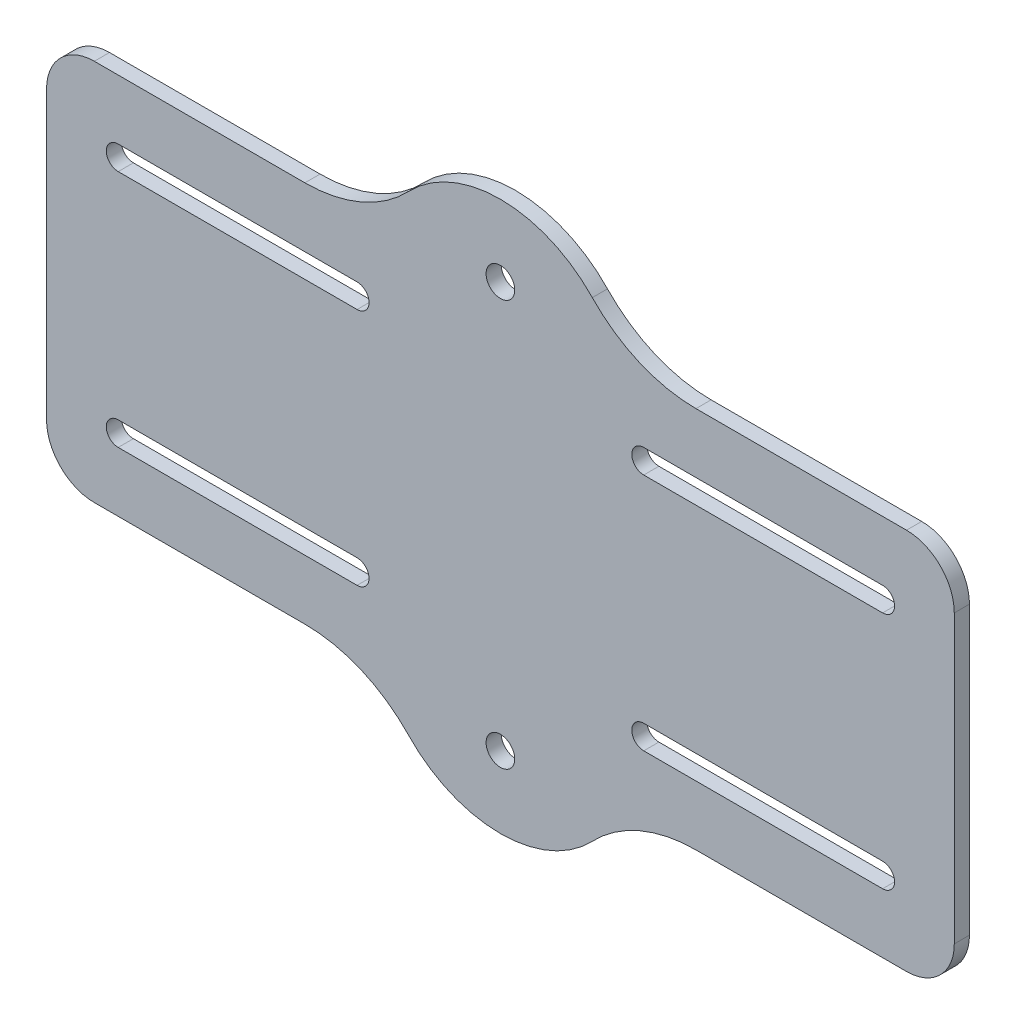
SolidWorks part; units mm, degrees
ref_plane "Front Plane" through (0, 0, 0) normal (0, 0, 1) x (1, 0, 0)
ref_plane "Top Plane" through (0, 0, 0) normal (0, 1, 0) x (1, 0, 0)
ref_plane "Right Plane" through (0, 0, 0) normal (1, 0, 0) x (0, 0, -1)
sketch "Sketch1" plane through (0, 0, 0) normal (0, 0, 1) x (1, 0, 0)
  line L0 (30, 25) -> (80, 25) construction
  line L1 (-95, -40) -> (-25, -40)
  line L2 (-95, -40) -> (-95, 40)
  line L3 (-95, 40) -> (-25, 40)
  line L4 (95, -40) -> (95, 40)
  line L9 (-95, 0) -> (95, 0) construction
  line L10 (0, 57.5) -> (0, -57.5) construction
  line L11 (30, 27.5) -> (80, 27.5)
  line L14 (30, 22.5) -> (80, 22.5)
  line L17 (30, -25) -> (80, -25) construction
  line L20 (-95, 0) -> (95, 0) construction
  line L21 (30, -27.5) -> (80, -27.5)
  line L22 (30, -22.5) -> (80, -22.5)
  line L23 (-30, 25) -> (-80, 25) construction
  line L24 (-30, 27.5) -> (-80, 27.5)
  line L25 (-30, 22.5) -> (-80, 22.5)
  line L26 (-30, -25) -> (-80, -25) construction
  line L27 (-30, -27.5) -> (-80, -27.5)
  line L28 (-30, -22.5) -> (-80, -22.5)
  line L29 (10, 55.5493) -> (10, -55.5493) construction
  line L30 (-10, 55.5493) -> (-10, -55.5493) construction
  line L37 (25, 40) -> (95, 40)
  line L38 (25, -40) -> (95, -40)
  circle A8 centre (0, 42.5) radius 3
  circle A9 centre (0, -42.5) radius 3
  arc A23 (30, 27.5) -> (30, 22.5) centre (30, 25) ccw
  arc A24 (80, 22.5) -> (80, 27.5) centre (80, 25) ccw
  arc A25 (30, -27.5) -> (30, -22.5) centre (30, -25) cw
  arc A26 (80, -22.5) -> (80, -27.5) centre (80, -25) cw
  arc A27 (-30, 27.5) -> (-30, 22.5) centre (-30, 25) cw
  arc A28 (-80, 22.5) -> (-80, 27.5) centre (-80, 25) cw
  arc A29 (-30, -27.5) -> (-30, -22.5) centre (-30, -25) ccw
  arc A30 (-80, -22.5) -> (-80, -27.5) centre (-80, -25) ccw
  arc A31 (-25, 40) -> (25, 40) centre (0, 30.8929) cw
  arc A32 (-25, -40) -> (25, -40) centre (0, -30.8929) ccw
  point P0 (0, 0)
  point P8 (55, 25)
  point P14 (0, 0)
  point P21 (55, -25)
  point P28 (-55, 25)
  point P35 (-55, -25)
  point P49 (-10, -88.3435)
  point P55 (-10, -82.0596)
  point P56 (-10, 55.5493)
  point P57 (-10, -55.5493)
  point P58 (10, -55.5493)
  point P59 (0, -57.5)
  point P60 (10, 55.5493)
  point P61 (0, 22.5)
  dimension "D8" = 6
  dimension "D4" = 50
  dimension "D5" = 15
  dimension "D6" = 20
  dimension "D9" = 20
  dimension "D1" = 80
  dimension "D2" = 50
  dimension "D3" = 5
  dimension "D7" = 85
  dimension "D10" = 50
  dimension "D11" = 15
extrude "Boss-Extrude1" add sketch "Sketch1" along normal blind 3.175
fillet "Fillet1" radius 10 4 edges at (-95, -40, 1.5875) (-95, 40, 1.5875) (95, -40, 1.5875) (95, 40, 1.5875)
fillet "Fillet2" radius 30 4 edges at (25, -40, 1.5875) (-25, -40, 1.5875) (25, 40, 1.5875) (-25, 40, 1.5875)
